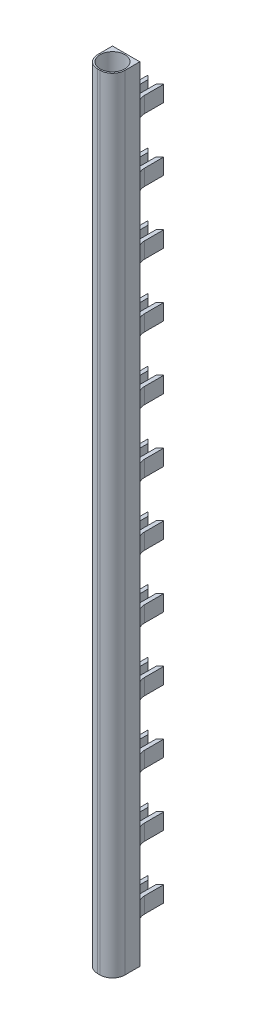
SolidWorks part; units mm, degrees
material "Miedź"
ref_plane "Front Plane" through (0, 0, 0) normal (0, 0, 1) x (1, 0, 0)
ref_plane "Top Plane" through (0, 0, 0) normal (0, 1, 0) x (1, 0, 0)
ref_plane "Right Plane" through (0, 0, 0) normal (1, 0, 0) x (0, 0, -1)
sketch "Szkic1" plane through (0, 0, 0) normal (0, 1, 0) x (1, 0, 0)
  line L1 (-0.55, -0.55) -> (0.55, -0.55)
  line L2 (-0.55, -0.55) -> (-0.55, 0.55)
  line L3 (-0.55, 0.55) -> (0.55, 0.55)
  line L4 (0.55, -0.55) -> (0.55, 0.55)
  line L5 (-0.55, -0.55) -> (0.55, 0.55) construction
  line L6 (-0.55, 0.55) -> (0.55, -0.55) construction
extrude "Dodanie-wyciągnięcie1" add sketch "Szkic1" along normal blind 31.58
sketch "Szkic2" plane through (0, 31.58, 0) normal (0, 1, 0) x (1, 0, 0)
  circle A0 centre (0, 0) radius 0.5
extrude "Wytnij-wyciągnięcie1" cut sketch "Szkic2" against normal blind 31.58
fillet "Zaokrąglenie1" radius 0.5 2 edges at (0.55, 15.79, 0.55) (-0.55, 15.79, 0.55)
sketch "Szkic3" plane through (0, 0, -0.55) normal (0, 0, -1) x (-1, 0, 0)
  line L0 (0, 0) -> (0, 1.5) construction
  line L1 (0, 1.5) -> (0, 2.14) construction
  line L2 (0, 2.14) -> (0, 4.04) construction
  line L3 (0, 4.04) -> (0, 4.68) construction
  line L4 (0, 4.68) -> (0, 6.58) construction
  line L5 (0, 6.58) -> (0, 7.22) construction
  line L6 (0, 7.22) -> (0, 9.12) construction
  line L7 (0, 9.12) -> (0, 9.76) construction
  line L8 (0, 9.76) -> (0, 11.66) construction
  line L9 (0, 11.66) -> (0, 12.3) construction
  line L10 (0, 12.3) -> (0, 14.2) construction
  line L11 (0, 14.2) -> (0, 14.84) construction
  line L12 (0, 14.84) -> (0, 16.74) construction
  line L13 (0, 16.74) -> (0, 17.38) construction
  line L14 (0, 17.38) -> (0, 19.28) construction
  line L15 (0, 19.28) -> (0, 19.92) construction
  line L16 (0, 19.92) -> (0, 21.82) construction
  line L17 (0, 21.82) -> (0, 22.46) construction
  line L18 (0, 22.46) -> (0, 24.36) construction
  line L19 (0, 24.36) -> (0, 25) construction
  line L20 (0, 25) -> (0, 26.9) construction
  line L21 (0, 26.9) -> (0, 27.54) construction
  line L22 (0, 27.54) -> (0, 29.44) construction
  line L23 (0, 29.44) -> (0, 30.08) construction
  line L24 (0, 30.08) -> (0, 31.58) construction
  line L25 (-0.55, 31.58) -> (0.55, 31.58) construction
  line L26 (0, 1.82) -> (-0.3177, 1.82)
  line L27 (-0.3177, 1.82) -> (0.3191, 1.82)
  line L28 (-0.3177, 1.82) -> (-0.3177, 31.58) construction
  line L29 (0.3191, 1.82) -> (0.3191, 31.58) construction
  line L30 (0, 1.5) -> (-0.3177, 1.5) construction
  line L31 (-0.3177, 1.5) -> (0.3191, 1.5) construction
  line L32 (-0.1588, 1.5) -> (-0.1588, 31.58) construction
  line L33 (0, 1.5) -> (0.3191, 1.5) construction
  line L34 (0.1596, 1.5) -> (0.1596, 31.58) construction
  line L36 (-0.3177, 1.5) -> (-0.1588, 1.5)
  line L37 (-0.3177, 1.5) -> (-0.3177, 2.14)
  line L38 (-0.3177, 2.14) -> (-0.1588, 2.14)
  line L39 (-0.1588, 1.5) -> (-0.1588, 2.14)
  line L40 (0.3191, 1.5) -> (0.1596, 1.5)
  line L41 (0.3191, 1.5) -> (0.3191, 2.14)
  line L42 (0.3191, 2.14) -> (0.1596, 2.14)
  line L43 (0.1596, 1.5) -> (0.1596, 2.14)
  line L44 (-0.3177, 4.04) -> (-0.1588, 4.04)
  line L45 (-0.3177, 4.04) -> (-0.3177, 4.68)
  line L46 (-0.3177, 4.68) -> (-0.1588, 4.68)
  line L47 (-0.1588, 4.04) -> (-0.1588, 4.68)
  line L48 (0.3191, 4.04) -> (0.1596, 4.04)
  line L49 (0.3191, 4.04) -> (0.3191, 4.68)
  line L50 (0.3191, 4.68) -> (0.1596, 4.68)
  line L51 (0.1596, 4.04) -> (0.1596, 4.68)
  line L52 (-0.3177, 6.58) -> (-0.1588, 6.58)
  line L53 (-0.3177, 6.58) -> (-0.3177, 7.22)
  line L54 (-0.3177, 7.22) -> (-0.1588, 7.22)
  line L55 (-0.1588, 6.58) -> (-0.1588, 7.22)
  line L56 (0.3191, 6.58) -> (0.1596, 6.58)
  line L57 (0.3191, 6.58) -> (0.3191, 7.22)
  line L58 (0.3191, 7.22) -> (0.1596, 7.22)
  line L59 (0.1596, 6.58) -> (0.1596, 7.22)
  line L60 (-0.3177, 9.12) -> (-0.1588, 9.12)
  line L61 (-0.3177, 9.12) -> (-0.3177, 9.76)
  line L62 (-0.3177, 9.76) -> (-0.1588, 9.76)
  line L63 (-0.1588, 9.12) -> (-0.1588, 9.76)
  line L64 (0.3191, 9.12) -> (0.1596, 9.12)
  line L65 (0.3191, 9.12) -> (0.3191, 9.76)
  line L66 (0.3191, 9.76) -> (0.1596, 9.76)
  line L67 (0.1596, 9.12) -> (0.1596, 9.76)
  line L68 (-0.3177, 11.66) -> (-0.1588, 11.66)
  line L69 (-0.3177, 11.66) -> (-0.3177, 12.3)
  line L70 (-0.3177, 12.3) -> (-0.1588, 12.3)
  line L71 (-0.1588, 11.66) -> (-0.1588, 12.3)
  line L72 (0.3191, 11.66) -> (0.1596, 11.66)
  line L73 (0.3191, 11.66) -> (0.3191, 12.3)
  line L74 (0.3191, 12.3) -> (0.1596, 12.3)
  line L75 (0.1596, 11.66) -> (0.1596, 12.3)
  line L76 (-0.3177, 14.2) -> (-0.1588, 14.2)
  line L77 (-0.3177, 14.2) -> (-0.3177, 14.84)
  line L78 (-0.3177, 14.84) -> (-0.1588, 14.84)
  line L79 (-0.1588, 14.2) -> (-0.1588, 14.84)
  line L80 (0.3191, 14.2) -> (0.1596, 14.2)
  line L81 (0.3191, 14.2) -> (0.3191, 14.84)
  line L82 (0.3191, 14.84) -> (0.1596, 14.84)
  line L83 (0.1596, 14.2) -> (0.1596, 14.84)
  line L84 (-0.3177, 16.74) -> (-0.1588, 16.74)
  line L85 (-0.3177, 16.74) -> (-0.3177, 17.38)
  line L86 (-0.3177, 17.38) -> (-0.1588, 17.38)
  line L87 (-0.1588, 16.74) -> (-0.1588, 17.38)
  line L88 (0.3191, 16.74) -> (0.1596, 16.74)
  line L89 (0.3191, 16.74) -> (0.3191, 17.38)
  line L90 (0.3191, 17.38) -> (0.1596, 17.38)
  line L91 (0.1596, 16.74) -> (0.1596, 17.38)
  line L92 (-0.3177, 19.28) -> (-0.1588, 19.28)
  line L93 (-0.3177, 19.28) -> (-0.3177, 19.92)
  line L94 (-0.3177, 19.92) -> (-0.1588, 19.92)
  line L95 (-0.1588, 19.28) -> (-0.1588, 19.92)
  line L96 (0.3191, 19.28) -> (0.1596, 19.28)
  line L97 (0.3191, 19.28) -> (0.3191, 19.92)
  line L98 (0.3191, 19.92) -> (0.1596, 19.92)
  line L99 (0.1596, 19.28) -> (0.1596, 19.92)
  line L100 (-0.3177, 21.82) -> (-0.1588, 21.82)
  line L101 (-0.3177, 21.82) -> (-0.3177, 22.46)
  line L102 (-0.3177, 22.46) -> (-0.1588, 22.46)
  line L103 (-0.1588, 21.82) -> (-0.1588, 22.46)
  line L104 (0.3191, 21.82) -> (0.1596, 21.82)
  line L105 (0.3191, 21.82) -> (0.3191, 22.46)
  line L106 (0.3191, 22.46) -> (0.1596, 22.46)
  line L107 (0.1596, 21.82) -> (0.1596, 22.46)
  line L108 (-0.3177, 24.36) -> (-0.1588, 24.36)
  line L109 (-0.3177, 24.36) -> (-0.3177, 25)
  line L110 (-0.3177, 25) -> (-0.1588, 25)
  line L111 (-0.1588, 24.36) -> (-0.1588, 25)
  line L112 (0.3191, 24.36) -> (0.1596, 24.36)
  line L113 (0.3191, 24.36) -> (0.3191, 25)
  line L114 (0.3191, 25) -> (0.1596, 25)
  line L115 (0.1596, 24.36) -> (0.1596, 25)
  line L116 (-0.3177, 26.9) -> (-0.1588, 26.9)
  line L117 (-0.3177, 26.9) -> (-0.3177, 27.54)
  line L118 (-0.3177, 27.54) -> (-0.1588, 27.54)
  line L119 (-0.1588, 26.9) -> (-0.1588, 27.54)
  line L120 (0.3191, 26.9) -> (0.1596, 26.9)
  line L121 (0.3191, 26.9) -> (0.3191, 27.54)
  line L122 (0.3191, 27.54) -> (0.1596, 27.54)
  line L123 (0.1596, 26.9) -> (0.1596, 27.54)
  line L124 (-0.3177, 29.44) -> (-0.1588, 29.44)
  line L125 (-0.3177, 29.44) -> (-0.3177, 30.08)
  line L126 (-0.3177, 30.08) -> (-0.1588, 30.08)
  line L127 (-0.1588, 29.44) -> (-0.1588, 30.08)
  line L128 (0.3191, 29.44) -> (0.1596, 29.44)
  line L129 (0.3191, 29.44) -> (0.3191, 30.08)
  line L130 (0.3191, 30.08) -> (0.1596, 30.08)
  line L131 (0.1596, 29.44) -> (0.1596, 30.08)
extrude "Dodanie-wyciągnięcie2" add sketch "Szkic3" along normal blind 1.3 contours L36 L39 L27 L37 | L27 L39 L38 L37 | L43 L40 L41 L27 | L43 L27 L41 L42 | L44 L47 L46 L45 | L51 L48 L49 L50 | L52 L55 L54 L53 | L59 L56 L57 L58 | L60 L63 L62 L61 | L67 L64 L65 L66 | L68 L71 L70 L69 | L75 L72 L73 L74 | L76 L79 L78 L77 | L83 L80 L81 L82 | L84 L87 L86 L85 | L91 L88 L89 L90 | L92 L95 L94 L93 | L99 L96 L97 L98 | L100 L103 L102 L101 | L107 L104 L105 L106 | L108 L111 L110 L109 | L115 L112 L113 L114 | L116 L119 L118 L117 | L123 L120 L121 L122 | L124 L127 L126 L125 | L131 L128 L129 L130 region at (0.2383, 1.66, -0.55) region at (0.2383, 1.98, -0.55) region at (-0.2393, 1.98, -0.55) region at (-0.2393, 1.66, -0.55) region at (0.2383, 4.36, -0.55) region at (-0.2393, 4.36, -0.55) region at (0.2383, 6.9, -0.55) region at (-0.2393, 6.9, -0.55) region at (0.2383, 9.44, -0.55) region at (-0.2393, 9.44, -0.55) region at (0.2383, 11.98, -0.55) region at (-0.2393, 11.98, -0.55) region at (0.2383, 14.52, -0.55) region at (-0.2393, 14.52, -0.55) region at (0.2383, 17.06, -0.55) region at (-0.2393, 17.06, -0.55) region at (0.2383, 19.6, -0.55) region at (-0.2393, 19.6, -0.55) region at (0.2383, 22.14, -0.55) region at (-0.2393, 22.14, -0.55) region at (0.2383, 24.68, -0.55) region at (-0.2393, 24.68, -0.55) region at (0.2383, 27.22, -0.55) region at (-0.2393, 27.22, -0.55) region at (0.2383, 29.76, -0.55) region at (-0.2393, 29.76, -0.55)
fillet "Zaokrąglenie2" radius 0.5 24 edges at (0.3177, 29.76, -0.55) (0.3177, 27.22, -0.55) (0.3177, 24.68, -0.55) (0.3177, 22.14, -0.55) (0.3177, 19.6, -0.55) (0.3177, 17.06, -0.55) (0.3177, 14.52, -0.55) (0.3177, 11.98, -0.55) (0.3177, 9.44, -0.55) (0.3177, 6.9, -0.55) (0.3177, 4.36, -0.55) (-0.3191, 29.76, -0.55) (-0.3191, 27.22, -0.55) (-0.3191, 24.68, -0.55) (-0.3191, 22.14, -0.55) (-0.3191, 19.6, -0.55) (-0.3191, 17.06, -0.55) (-0.3191, 14.52, -0.55) (-0.3191, 11.98, -0.55) (-0.3191, 9.44, -0.55) (-0.3191, 6.9, -0.55) (-0.3191, 4.36, -0.55) (0.3177, 1.82, -0.55) (-0.3191, 1.82, -0.55)
chamfer "Sfazowanie1" distance 0.25 angle 45 24 edges at (-0.1596, 29.76, -1.85) (0.1588, 29.76, -1.85) (-0.1596, 27.22, -1.85) (0.1588, 27.22, -1.85) (-0.1596, 24.68, -1.85) (0.1588, 24.68, -1.85) (-0.1596, 22.14, -1.85) (0.1588, 22.14, -1.85) (-0.1596, 19.6, -1.85) (0.1588, 19.6, -1.85) (-0.1596, 17.06, -1.85) (0.1588, 17.06, -1.85) (-0.1596, 14.52, -1.85) (0.1588, 14.52, -1.85) (-0.1596, 11.98, -1.85) (0.1588, 11.98, -1.85) (-0.1596, 9.44, -1.85) (0.1588, 9.44, -1.85) (-0.1596, 6.9, -1.85) (0.1588, 6.9, -1.85) (-0.1596, 4.36, -1.85) (0.1588, 4.36, -1.85) (-0.1596, 1.82, -1.85) (0.1588, 1.82, -1.85)
fillet "Zaokrąglenie3" radius 0.01 24 edges at (0.3177, 29.76, -1.7588) (-0.3191, 29.76, -1.7596) (0.3177, 27.22, -1.7588) (-0.3191, 27.22, -1.7596) (0.3177, 24.68, -1.7588) (-0.3191, 24.68, -1.7596) (0.3177, 22.14, -1.7588) (-0.3191, 22.14, -1.7596) (0.3177, 19.6, -1.7588) (-0.3191, 19.6, -1.7596) (0.3177, 17.06, -1.7588) (-0.3191, 17.06, -1.7596) (0.3177, 14.52, -1.7588) (-0.3191, 14.52, -1.7596) (0.3177, 11.98, -1.7588) (-0.3191, 11.98, -1.7596) (-0.3191, 9.44, -1.7596) (0.3177, 9.44, -1.7588) (0.3177, 6.9, -1.7588) (-0.3191, 6.9, -1.7596) (0.3177, 1.82, -1.7588) (-0.3191, 4.36, -1.7596) (0.3177, 4.36, -1.7588) (-0.3191, 1.82, -1.7596)
